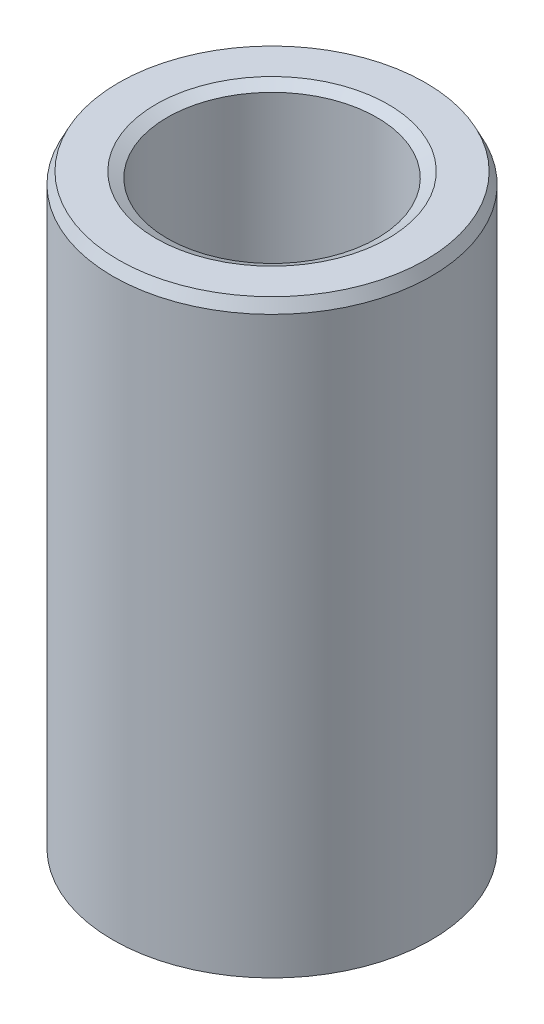
SolidWorks part; units mm, degrees
ref_plane "Front Plane" through (0, 0, 0) normal (0, 0, 1) x (1, 0, 0)
ref_plane "Top Plane" through (0, 0, 0) normal (0, 1, 0) x (1, 0, 0)
ref_plane "Right Plane" through (0, 0, 0) normal (1, 0, 0) x (0, 0, -1)
sketch "Sketch1" plane through (0, 0, 0) normal (0, 1, 0) x (1, 0, 0)
  circle A0 centre (0, 0) radius 50
  dimension "SLEEVE_OD" = 100
extrude "Boss-Extrude1" add sketch "Sketch1" along normal blind 185.8351
sketch "Sketch2" plane through (0, 0, 0) normal (0, 1, 0) x (1, 0, 0)
  circle A0 centre (0, 0) radius 32.9258
  dimension "BORE_D" = 65.8516
extrude "Cut-Extrude1" cut sketch "Sketch2" along normal through all
chamfer "Chamfer1" distance 3.5576 angle 26.585 4 edges at (0, 185.8351, 32.9258) (0, 0, 32.9258) (0, 0, 50) (0, 185.8351, 50) first distance on face at (0, 185.8351, 32.9258) first distance on face at (0, 0, 32.9258) first distance on face at (0, 185.8351, 50)
